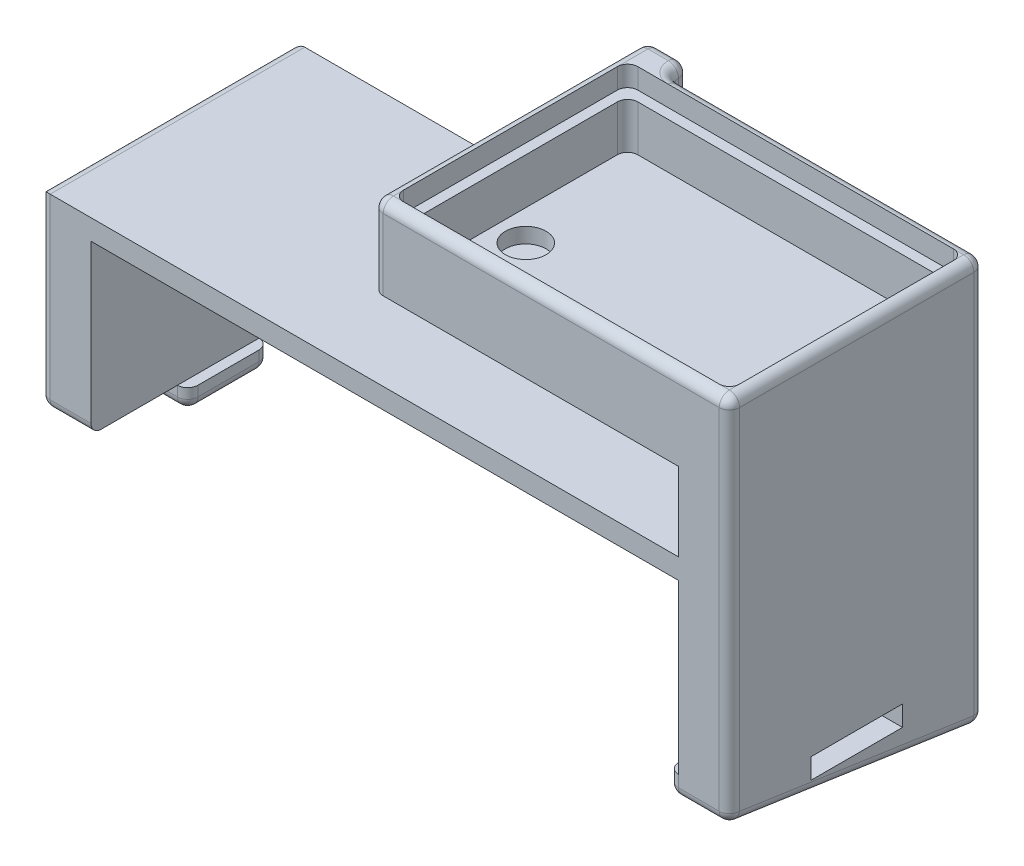
SolidWorks part; units mm, degrees
ref_plane "Front Plane" through (0, 0, 0) normal (0, 0, 1) x (1, 0, 0)
ref_plane "Top Plane" through (0, 0, 0) normal (0, 1, 0) x (1, 0, 0)
ref_plane "Right Plane" through (0, 0, 0) normal (1, 0, 0) x (0, 0, -1)
sketch "Sketch1" plane through (0, 0, 0) normal (0, 0, 1) x (1, 0, 0)
  line L0 (0, 0) -> (30, 0)
  line L1 (30, 0) -> (30, -7.7)
  line L2 (30, -7.7) -> (-32.7, -7.7)
  line L3 (-32.7, -7.7) -> (-32.7, -26.2)
  line L4 (-32.7, -26.2) -> (35, -26.2)
  line L5 (35, -26.2) -> (35, 8)
  line L6 (35, 8) -> (0, 8)
  line L7 (0, 8) -> (0, 0)
  dimension "D1" = 7.7
  dimension "D2" = 30
  dimension "D3" = 35
  dimension "D4" = 67.7
  dimension "D5" = 8
  dimension "D6" = 18.5
extrude "Boss-Extrude1" add sketch "Sketch1" along normal blind 25
sketch "Sketch2" plane through (0, 0, 25) normal (0, 0, 1) x (1, 0, 0)
  line L0 (-32.7, -26.2) -> (35, -26.2) construction
  line L1 (30, -26.2) -> (-27.7, -26.2)
  line L2 (30, -26.2) -> (30, -9.7)
  line L3 (30, -9.7) -> (-27.7, -9.7)
  line L4 (-27.7, -26.2) -> (-27.7, -9.7)
  line L5 (35, -26.2) -> (35, 8) construction
  dimension "D1" = 57.7
  dimension "D2" = 5
  dimension "D3" = 16.5
extrude "Cut-Extrude1" cut sketch "Sketch2" against normal through all
sketch "Sketch3" plane through (0, 8, 0) normal (0, 1, 0) x (1, 0, 0)
  line L0 (35, -25) -> (35, 0) construction
  line L1 (2, -2) -> (33, -2)
  line L2 (2, -2) -> (2, -23)
  line L3 (2, -23) -> (33, -23)
  line L4 (33, -2) -> (33, -23)
  line L5 (0, -25) -> (0, 0) construction
  line L6 (35, 0) -> (0, 0) construction
  line L7 (35, -25) -> (0, -25) construction
  dimension "D1" = 2
  dimension "D2" = 2
  dimension "D3" = 2
  dimension "D4" = 2
extrude "Cut-Extrude2" cut sketch "Sketch3" against normal blind 6.5
sketch "Sketch4" plane through (0, -26.2, 0) normal (0, -1, 0) x (1, 0, 0)
  line L0 (35, 12.5) -> (35.1733, 12.5) construction
  line L1 (35, 25) -> (35, 0) construction
  line L2 (30, 0) -> (30, 25) construction
  circle A0 centre (30.5, 12.5) radius 2
  dimension "D1" = 4
  dimension "D2" = 0.5
extrude "Cut-Extrude3" cut sketch "Sketch4" against normal up to surface (27.7 mm away) up to face at (17.5, 1.5, 12.5)
sketch "Sketch5" plane through (0, 1.5, 0) normal (0, 1, 0) x (1, 0, 0)
  line L1 (35, 0) -> (0, 0) construction
  line L2 (30, -25) -> (30, -14.4365) construction
  circle A0 centre (5, -15) radius 2
  dimension "D1" = 4
  dimension "D2" = 25
  dimension "D3" = 15
extrude "Cut-Extrude4" cut sketch "Sketch5" against normal up to surface (1.5 mm away) up to face at (19.75, 0, 12.5)
sketch "Sketch6" plane through (0, -26.2, 0) normal (0, -1, 0) x (1, 0, 0)
  line L0 (35, 25) -> (35, 0) construction
  line L1 (35, 25) -> (29, 25)
  line L2 (35, 25) -> (35, 17)
  line L3 (35, 17) -> (29, 17)
  line L4 (29, 25) -> (29, 17)
  line L5 (35, 0) -> (29, 0)
  line L6 (35, 0) -> (35, 8)
  line L7 (35, 8) -> (29, 8)
  line L8 (29, 0) -> (29, 8)
  line L9 (-32.7, 25) -> (-32.7, 0) construction
  line L10 (-32.7, 16.5) -> (-26.7, 16.5)
  line L11 (-32.7, 16.5) -> (-32.7, 8.5)
  line L12 (-32.7, 8.5) -> (-26.7, 8.5)
  line L13 (-26.7, 16.5) -> (-26.7, 8.5)
  line L14 (35, 12.5) -> (36.5966, 12.5) construction
  dimension "D1" = 8
  dimension "D2" = 6
extrude "Boss-Extrude2" add sketch "Sketch6" along normal blind 2
sketch "Sketch7" plane through (0, 0, 0) normal (0, 0, 1) x (1, 0, 0)
  line L0 (0, 8) -> (0, -9.7)
  line L1 (35, 8) -> (0, 8) construction
  line L3 (30, -9.7) -> (-27.7, -9.7) construction
  line L4 (4, -9.7) -> (4, 8)
  line L5 (4, 8) -> (0, 8)
  line L20 (30, -9.7) -> (30, -26.2)
  line L21 (30, -26.2) -> (29, -26.2)
  line L22 (29, -26.2) -> (29, -28.2)
  line L23 (29, -28.2) -> (35, -28.2)
  line L24 (35, -28.2) -> (35, 8)
  line L25 (35, 8) -> (0, 8)
  line L26 (0, 8) -> (0, 0)
  line L27 (0, 0) -> (30, 0)
  line L28 (30, 0) -> (30, -7.7)
  line L29 (30, -7.7) -> (-32.7, -7.7)
  line L30 (-32.7, -7.7) -> (-32.7, -26.2)
  line L31 (-32.7, -26.2) -> (-27.7, -26.2)
  line L32 (-27.7, -26.2) -> (-27.7, -9.7)
  line L33 (-27.7, -9.7) -> (30, -9.7)
  line L47 (0, -9.7) -> (4, -9.7)
  dimension "D2" = 4
  dimension "D1" = 0
sketch "Sketch8" plane through (35, 0, 0) normal (1, 0, 0) x (0, 0, -1)
  line L0 (-25, -28.2) -> (0, -31.86)
  line L1 (0, -31.86) -> (0, -28.2)
  line L3 (-25, -28.2) -> (-25, 8) construction
  line L4 (-25, -28.2) -> (0, -28.2)
  line L5 (0, -28.2) -> (-8, -28.2) construction
  dimension "D1" = 3.66
  dimension "D2" = 8.329
extrude "Boss-Extrude4" add sketch "Sketch8" against normal up to surface (6 mm away) up to face at (29, -27.2, 4)
sketch "Sketch9" plane through (0, 8, 0) normal (0, 1, 0) x (1, 0, 0)
  line L0 (33, -23) -> (33, -2) construction
  line L1 (34, -24) -> (1, -24)
  line L2 (34, -24) -> (34, -1)
  line L3 (34, -1) -> (1, -1)
  line L4 (1, -24) -> (1, -1)
  line L5 (2, -23) -> (33, -23) construction
  line L6 (2, -2) -> (2, -23) construction
  line L7 (33, -2) -> (2, -2) construction
  dimension "D1" = 1
  dimension "D2" = 1
  dimension "D3" = 1
  dimension "D4" = 1
extrude "Cut-Extrude5" cut sketch "Sketch9" against normal blind 2
fillet "Fillet1" radius 1 8 edges at (34, 7, 1) (1, 7, 1) (1, 7, 24) (34, 7, 24) (33, 3.75, 2) (2, 3.75, 2) (2, 3.75, 23) (33, 3.75, 23)
sketch "Sketch10" plane through (-27.7, 0, 0) normal (1, 0, 0) x (0, 0, -1)
  line L0 (-12.5, -9.7) -> (-12.5, -2.753) construction
  line L1 (0, -9.7) -> (-25, -9.7) construction
  circle A0 centre (-14, -12.05) radius 1
  circle A1 centre (-11, -12.05) radius 1
  dimension "D2" = 2
  dimension "D3" = 2
  dimension "D1" = 3
  dimension "D4" = 2.35
extrude "Boss-Extrude5" add sketch "Sketch10" along normal blind 1.5
fillet "Fillet3" radius 1 2 edges at (-26.2, -12.05, 13) (-26.2, -12.05, 10)
extrude "Boss-Extrude6" add sketch "Sketch7" against normal blind 2
fillet "Fillet4" radius 1 34 edges at (-29.7, -28.2, 16.5) (-26.7, -28.2, 12.5) (-29.7, -28.2, 8.5) (-32.7, -28.2, 12.5) (32, -28.2, 25) (35, -30.03, 12.5) (32, -31.86, 0) (29, -30.03, 12.5) (-30.2, -26.2, 0) (-30.2, -26.2, 25) (29, -29.03, 0) (29, -27.2, 25) (-26.7, -27.2, 8.5) (-26.7, -27.2, 16.5) (-32.7, -27.2, 8.5) (-32.7, -27.2, 16.5) (-32.7, -26.2, 4.25) (-32.7, -26.2, 20.75) (-32.7, -16.95, 25) (-32.7, -7.7, 12.5) (-32.7, -16.95, 0) (4, -0.85, -2) (2, -9.7, -2) (2, 8, -2) (0, -0.85, -2) (0, 8, 11.5) (0, 4, 25) (17.5, 8, 25) (35, 8, 12.5) (35, -11.93, 0) (35, -10.1, 25)
